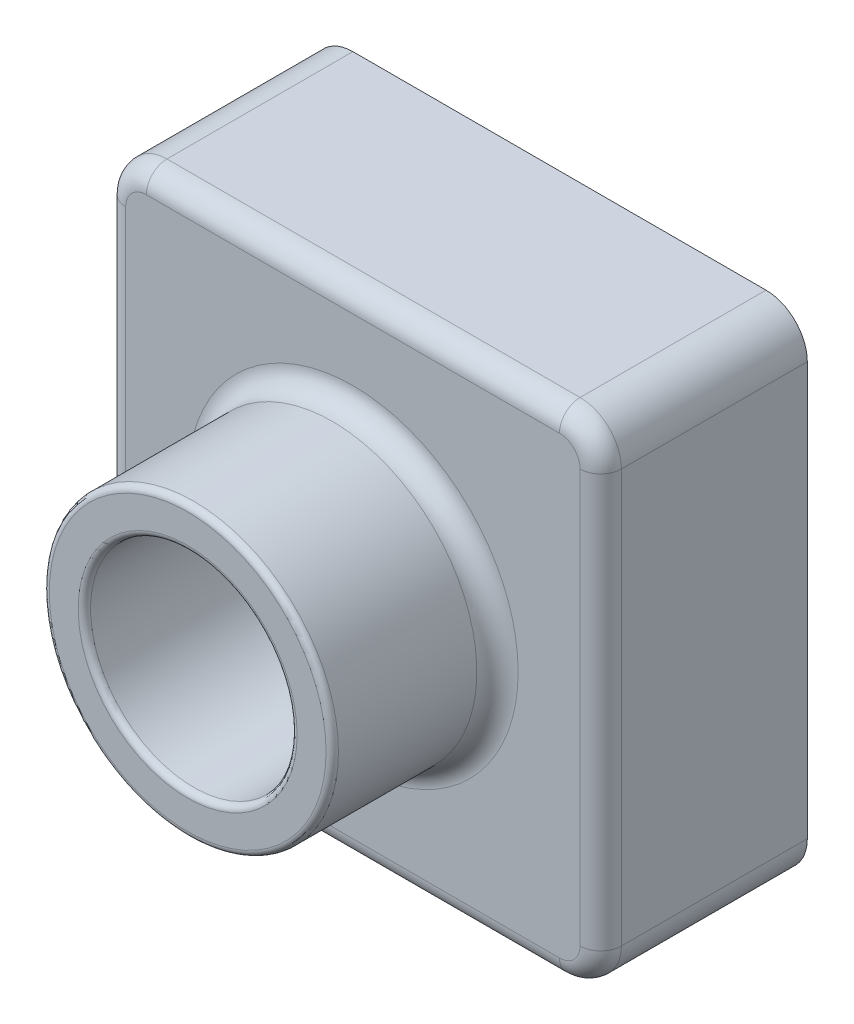
SolidWorks part; units mm, degrees
ref_plane "Спереди" through (0, 0, 0) normal (0, 0, 1) x (1, 0, 0)
ref_plane "Сверху" through (0, 0, 0) normal (0, 1, 0) x (1, 0, 0)
ref_plane "Справа" through (0, 0, 0) normal (1, 0, 0) x (0, 0, -1)
sketch "Эскиз1" plane through (0, 0, 0) normal (0, 0, 1) x (1, 0, 0)
  line L1 (0, 0) -> (120, 0)
  line L2 (0, 0) -> (0, 120)
  line L3 (0, 120) -> (120, 120)
  line L4 (120, 0) -> (120, 120)
  dimension "D1" = 120
  dimension "D2" = 120
extrude "Бобышка-Вытянуть1" add sketch "Эскиз1" along normal blind 50
sketch "Эскиз2" plane through (0, 0, 50) normal (0, 0, 1) x (1, 0, 0)
  line L0 (0, 0) -> (120, 0) construction
  line L1 (0, 120) -> (0, 0) construction
  circle A0 centre (60, 60) radius 35
  point P4 (0, 60)
  point P6 (36.9061, 102.9512)
  dimension "D3" = 70
  dimension "D1" = 60
  dimension "D2" = 60
extrude "Бобышка-Вытянуть2" add sketch "Эскиз2" along normal blind 40
sketch "Эскиз3" plane through (0, 0, 90) normal (0, 0, 1) x (1, 0, 0)
  circle A2 centre (60, 60) radius 25
  circle A3 centre (60, 60) radius 25
  dimension "D1" = 10
extrude "Вырез-Вытянуть1" cut sketch "Эскиз3" against normal through all
fillet "Скругление1" radius 5 1 edges at (95, 60, 50)
fillet "Скругление2" radius 5 4 edges at (0, 60, 50) (60, 0, 50) (120, 60, 50) (60, 120, 50)
fillet "Скругление3" radius 1.5 2 edges at (85, 60, 90) (95, 60, 90)
fillet "Скругление5" radius 10 8 edges at (118.5355, 118.5355, 48.5355) (1.4645, 118.5355, 48.5355) (1.4645, 1.4645, 48.5355) (118.5355, 1.4645, 48.5355) (120, 0, 22.5) (0, 0, 22.5) (0, 120, 22.5) (120, 120, 22.5)
shell "Оболочка1" thickness 2 removed face at (85, 60, 0)
